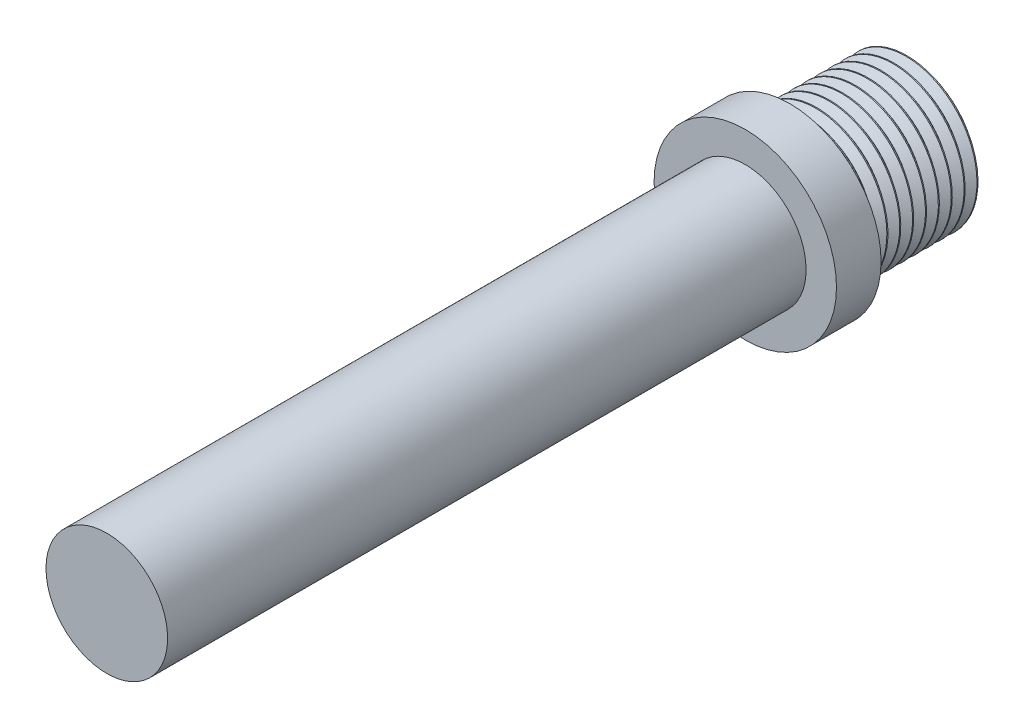
SolidWorks part; units mm, degrees
material "AISI 4130 Acero recocido a 865C"
ref_plane "Alzado" through (0, 0, 0) normal (0, 0, 1) x (1, 0, 0)
ref_plane "Planta" through (0, 0, 0) normal (0, 1, 0) x (1, 0, 0)
ref_plane "Vista lateral" through (0, 0, 0) normal (1, 0, 0) x (0, 0, -1)
sketch "Sk_Eje" plane through (0, 0, 0) normal (0, 1, 0) x (1, 0, 0)
  line L0 (172.5, -67.1) -> (179.645, -67.1)
  line L1 (179.645, -67.1) -> (179.645, -79.1)
  line L2 (179.645, -79.1) -> (181.5, -79.1)
  line L3 (181.5, -79.1) -> (181.5, -83.5)
  line L4 (181.5, -83.5) -> (178.5, -83.5)
  line L5 (178.5, -83.5) -> (178.5, -146.5)
  line L6 (178.5, -146.5) -> (172.5, -146.5)
  line L7 (172.5, -146.5) -> (172.5, -67.1)
  line L8 (172.5, -62.1) -> (172.5, -160) construction
revolve "Eje" add sketch "Sk_Eje" angle 360 about L8
ref_axis "Eje_pedal" through (172.5, 0, 146.5) along (0, 0, -1)
ref_plane "Plano_rosca" through (0, 0, 67.1) normal (0, 0, 1) x (1, 0, 0)
sketch "Sk_helice" plane through (0, 0, 67.1) normal (0, 0, 1) x (1, 0, 0)
  circle A0 centre (172.5, 0) radius 7.145
  dimension "DIAM1" = 14.29
curve "Helice_rosca" pitch 1.27 height 12 radius 7.145 left hand yes centre (172.5, 0, 67.1) axis (0, 0, 1) start towards (1, 0, 0)
sketch "Sk_filete" plane through (0, 0, 0) normal (0, 1, 0) x (1, 0, 0)
  line L0 (179.945, -66.295) -> (179.945, -67.905)
  line L1 (179.945, -67.905) -> (178.866, -67.1)
  line L2 (178.866, -67.1) -> (179.945, -66.295)
sweep "Rosca" cut profiles "Sk_filete" path "Helice_rosca" align with end faces yes
